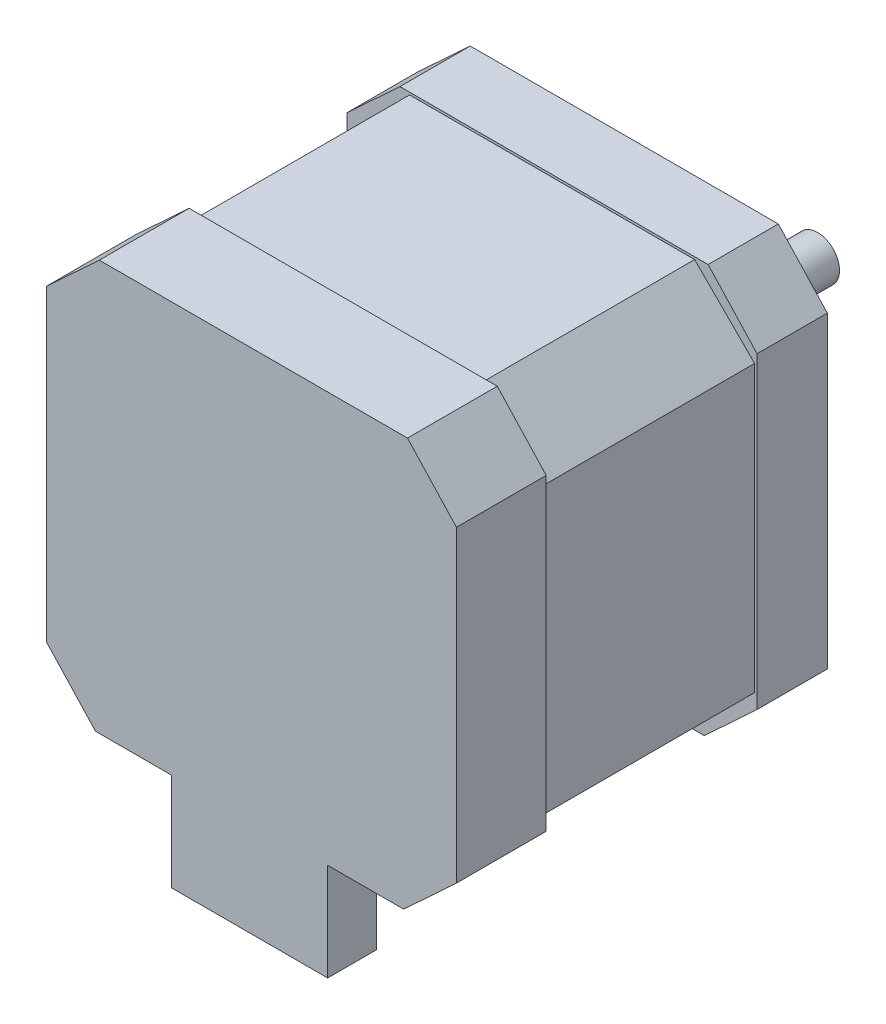
SolidWorks part; units mm, degrees
material "Ferro dúctil"
ref_plane "Plano frontal" through (0, 0, 0) normal (0, 0, 1) x (1, 0, 0)
ref_plane "Plano superior" through (0, 0, 0) normal (0, 1, 0) x (1, 0, 0)
ref_plane "Plano direito" through (0, 0, 0) normal (1, 0, 0) x (0, 0, -1)
sketch "Esboço1" plane through (0, 0, 0) normal (0, 0, 1) x (1, 0, 0)
  line L0 (-1.3818, -36.7436) -> (-36.7436, 1.3818)
  line L1 (-21, 21) -> (21, 21)
  line L2 (-21, 21) -> (-21, -21)
  line L3 (-21, -21) -> (21, -21)
  line L4 (21, 21) -> (21, -21)
  line L5 (-21, 21) -> (21, -21) construction
  line L6 (-21, -21) -> (21, 21) construction
  line L7 (-1.3818, -36.7436) -> (36.7436, -1.3818)
  line L8 (-36.7436, 1.3818) -> (1.3818, 36.7436)
  line L9 (36.7436, -1.3818) -> (1.3818, 36.7436)
  line L10 (-1.3818, -36.7436) -> (1.3818, 36.7436) construction
  line L11 (-36.7436, 1.3818) -> (36.7436, -1.3818) construction
  point P0 (0, 0)
  point P7 (0, 0)
  dimension "D1" = 42
  dimension "D2" = 52
extrude "Ressalto-extrusão1" add sketch "Esboço1" along normal blind 38 contours L4 L9 L1 L8 L2 L0 L3 L7 region at (0, 0, 0)
sketch "Esboço2" plane through (0, 0, 38) normal (0, 0, 1) x (1, 0, 0)
  line L1 (-20.75, -20.75) -> (20.75, -20.75)
  line L2 (-20.75, -20.75) -> (-20.75, 20.75)
  line L3 (-20.75, 20.75) -> (20.75, 20.75)
  line L4 (20.75, -20.75) -> (20.75, 20.75)
  line L5 (-20.75, -20.75) -> (20.75, 20.75) construction
  line L6 (-20.75, 20.75) -> (20.75, -20.75) construction
  line L7 (0, -35.3553) -> (-35.3553, 0)
  line L8 (0, -35.3553) -> (35.3553, 0)
  line L9 (-35.3553, 0) -> (0, 35.3553)
  line L10 (35.3553, 0) -> (0, 35.3553)
  line L11 (0, -35.3553) -> (0, 35.3553) construction
  line L12 (-35.3553, 0) -> (35.3553, 0) construction
  point P0 (0, 0)
  point P8 (-17.6777, 17.6777)
  point P9 (0, 0)
  dimension "D1" = 50
  dimension "D2" = 41.5
extrude "Corte-Extrusão-Fina1" cut sketch "Esboço2" against normal offset from surface (21.6 mm away) 7.2 from offset 9.2 thin contours L4 L10 L3 L9 L2 L7 L1 L8 up to face at (0, 0, 0) offset against normal yes thin type one direction wall 10
sketch "Esboço3" plane through (0, 0, 0) normal (0, 0, -1) x (-1, 0, 0)
  circle A0 centre (0, 0) radius 2.25
  dimension "D1" = 4.5
extrude "Ressalto-extrusão2" add sketch "Esboço3" along normal blind 20
sketch "Esboço4" plane through (0, 0, 0) normal (0, 0, -1) x (-1, 0, 0)
  circle A0 centre (0, 0) radius 10
  dimension "D1" = 20
extrude "Ressalto-extrusão3" add sketch "Esboço4" along normal blind 2
sketch "Esboço5" plane through (0, 0, 0) normal (0, 0, -1) x (-1, 0, 0)
  line L1 (15.5, 15.5) -> (-15.5, 15.5) construction
  line L2 (15.5, 15.5) -> (15.5, -15.5) construction
  line L3 (15.5, -15.5) -> (-15.5, -15.5) construction
  line L4 (-15.5, 15.5) -> (-15.5, -15.5) construction
  line L5 (15.5, 15.5) -> (-15.5, -15.5) construction
  line L6 (15.5, -15.5) -> (-15.5, 15.5) construction
  circle A0 centre (15.5, -15.5) radius 1.5
  circle A1 centre (-15.5, -15.5) radius 1.5
  circle A2 centre (-15.5, 15.5) radius 1.5
  circle A3 centre (15.5, 15.5) radius 1.5
  point P0 (0, 0)
  dimension "D1" = 3
  dimension "D2" = 31
extrude "Corte-extrusão1" cut sketch "Esboço5" against normal blind 10
sketch "Esboço7" plane through (0, -21, 0) normal (0, -1, 0) x (1, 0, 0)
  line L0 (-15.9842, 38) -> (15.5922, 38) construction
  line L1 (7.804, 33) -> (-8.196, 33)
  line L2 (7.804, 33) -> (7.804, 38)
  line L3 (7.804, 38) -> (-8.196, 38)
  line L4 (-8.196, 33) -> (-8.196, 38)
  line L5 (7.804, 33) -> (-8.196, 38) construction
  line L6 (7.804, 38) -> (-8.196, 33) construction
  line L7 (-15.9842, 0) -> (15.5922, 0) construction
  point P0 (-0.196, 35.5)
  point P7 (0, 0)
  point P10 (-0.196, 0)
  dimension "D1" = 5
  dimension "D2" = 16
extrude "Ressalto-extrusão4" add sketch "Esboço7" along normal blind 10
